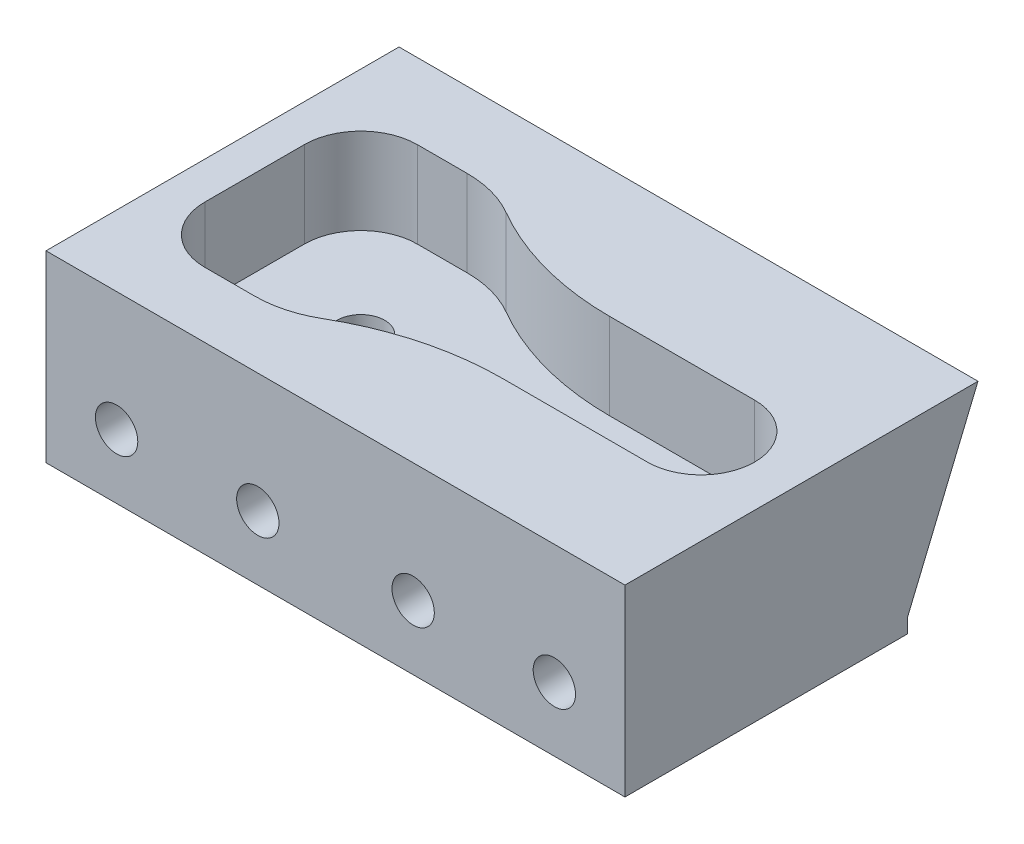
SolidWorks part; units mm, degrees
ref_plane "Front Plane" through (0, 0, 0) normal (0, 0, 1) x (1, 0, 0)
ref_plane "Top Plane" through (0, 0, 0) normal (0, 1, 0) x (1, 0, 0)
ref_plane "Right Plane" through (0, 0, 0) normal (1, 0, 0) x (0, 0, -1)
sketch "Sketch1" plane through (0, 0, 0) normal (0, 1, 0) x (1, 0, 0)
  line L1 (0, 0) -> (41, 0)
  line L2 (0, 0) -> (0, 25)
  line L3 (0, 25) -> (41, 25)
  line L4 (41, 0) -> (41, 25)
  dimension "D1" = 25
  dimension "D2" = 41
extrude "Boss-Extrude1" add sketch "Sketch1" along normal blind 13
sketch "Sketch2" plane through (0, 0, 0) normal (0, 0, 1) x (1, 0, 0)
  line L0 (0, 0) -> (41, 0) construction
  line L1 (0, 13) -> (0, 0) construction
  circle A0 centre (5, 4.545) radius 1.5
  dimension "D1" = 3
  dimension "D2" = 4.545
  dimension "D3" = 5
extrude "Cut-Extrude1" cut sketch "Sketch2" against normal through all
pattern_linear "LPattern1" count 2 spacing 10 along (1, 0, 0) of "Cut-Extrude1"
pattern_linear "LPattern3" count 2 spacing 21 along (1, 0, 0) of "Cut-Extrude1"
sketch "Sketch8" plane through (0, 0, 0) normal (0, 0, 1) x (1, 0, 0)
  line L0 (26, 4.545) -> (36, 4.545) construction
  circle A0 centre (36, 4.545) radius 1.5
  circle A2 centre (26, 4.545) radius 1.5 construction
  dimension "D1" = 10
extrude "Cut-Extrude5" cut sketch "Sketch8" against normal blind 8
sketch "Sketch3" plane through (0, 13, 0) normal (0, 1, 0) x (1, 0, 0)
  line L0 (34.25, 12.135) -> (10.16, 12.135) construction
  line L1 (34.25, 8.335) -> (10.16, 8.335)
  line L2 (34.25, 15.935) -> (10.16, 15.935)
  line L3 (0, 0) -> (41, 0) construction
  line L4 (0, 25) -> (0, 0) construction
  line L5 (10.16, 4.61) -> (6.635, 4.61)
  line L6 (10.16, 4.61) -> (10.16, 19.66)
  line L7 (10.16, 19.66) -> (6.635, 19.66)
  line L8 (2.635, 8.61) -> (2.635, 15.66)
  circle A1 centre (10.16, 12.135) radius 7.525
  arc A2 (34.25, 8.335) -> (34.25, 15.935) centre (34.25, 12.135) ccw
  arc A3 (10.16, 15.935) -> (10.16, 8.335) centre (10.16, 12.135) ccw
  arc A4 (6.635, 19.66) -> (2.635, 15.66) centre (6.635, 15.66) ccw
  arc A5 (6.635, 4.61) -> (2.635, 8.61) centre (6.635, 8.61) cw
  point P1 (22.205, 12.135)
  dimension "D2" = 15.05
  dimension "D6" = 4
  dimension "D1" = 12.135
  dimension "D3" = 7.6
  dimension "D4" = 10.16
  dimension "D5" = 24.09
  dimension "D8" = 31.615
extrude "Cut-Extrude2" cut sketch "Sketch3" against normal blind 6.1 contours L1 A2 L2 A1 | A1 L0 L6 L1 | L6 A1 L1 | A3 L6 A1 | L6 A3 | L0 A1 L2 L6 | L2 A1 L6 | L7 A4 L8 A1 | A5 L5 A1 L8 region at (13.7622, 13, -10.2797) region at (13.7622, 13, -13.9903) region at (17.6421, 13, -14.1629) region at (8.5472, 13, -12.135) region at (12.7025, 13, -17.462) region at (12.7025, 13, -6.808) region at (9.9917, 13, -6.4725) region at (4.6259, 13, -17.6691) region at (4.6259, 13, -6.6009)
hole_wizard "CBORE for M3 Hex Socket Head Cap Screw1" positions "Sketch6" profile "Sketch5" counterbore size "M3" standard "ISO" end condition through all
sketch "Sketch6" plane through (0, 0, 0) normal (0, -1, 0) x (-1, 0, 0)
  arc A2 (-16.655, 8.335) -> (-10.16, 4.61) centre (-10.16, 12.135) ccw construction
  arc A3 (-34.25, 15.935) -> (-34.25, 8.335) centre (-34.25, 12.135) ccw construction
  point P0 (-34.25, 12.135)
  point P2 (-10.16, 12.135)
sketch "Sketch5" plane through (34.25, 0, -12.135) normal (1, 0, 0) x (0, 0, -1)
  line L0 (0, 0) -> (0, 13)
  line L1 (0, 13) -> (1.7, 13)
  line L3 (1.7, 13) -> (1.7, 3.4)
  line L4 (1.7, 3.4) -> (3, 3.4)
  line L5 (3, 3.4) -> (3, 0)
  line L7 (3, 0) -> (0, 0)
  line L11 (0, -6.35) -> (0, 107.95) construction
  dimension "Thru Hole Dia." = 3.4
  dimension "Thru Hole Depth" = 13
  dimension "C'Bore Dia." = 6
  dimension "C'Bore Depth" = 3.4
fillet "Fillet1" radius 20 2 edges at (16.655, 9.95, -8.335) (16.655, 9.95, -15.935)
sketch "Sketch7" plane through (0, 0, 0) normal (-1, 0, 0) x (0, 0, 1)
  line L0 (-25, 13) -> (-20, 1)
  line L2 (-20, 1) -> (-20, 0)
  line L3 (-25, 0) -> (0, 0) construction
  line L4 (0, 13) -> (0, 0) construction
  dimension "D1" = 20
  dimension "D2" = 1
extrude "Cut-Extrude4" cut sketch "Sketch7" against normal through all and the other way through all flip side to cut
sketch "Sketch9" plane through (0, 3.4, 0) normal (0, -1, 0) x (1, 0, 0)
  line L1 (11.86, -9.135) -> (8.46, -9.135)
  line L2 (11.86, -9.135) -> (11.86, -15.135)
  line L3 (11.86, -15.135) -> (8.46, -15.135)
  line L4 (8.46, -9.135) -> (8.46, -15.135)
  circle A1 centre (10.16, -12.135) radius 1.7 construction
  circle A2 centre (10.16, -12.135) radius 3 construction
  circle M6 centre (10.16, -12.135) radius 3
extrude "Boss-Extrude3" add sketch "Sketch9" along normal blind 0.2 contours L4 M6 | L2 M6 region at (12.3911, 3.4, -12.135) region at (7.9289, 3.4, -12.135)
pattern_linear "LPattern2" count 2 spacing 24.09 along (1, 0, 0) of "Boss-Extrude3"
move or copy body "Body-Move/Copy1" [suppressed] bodies to move or copy 111
equation "\"D2@Sketch2\"=(8-2.39+3.48)/2"
equation "\"D1@Sketch3\"=10.46+3.35/2"
